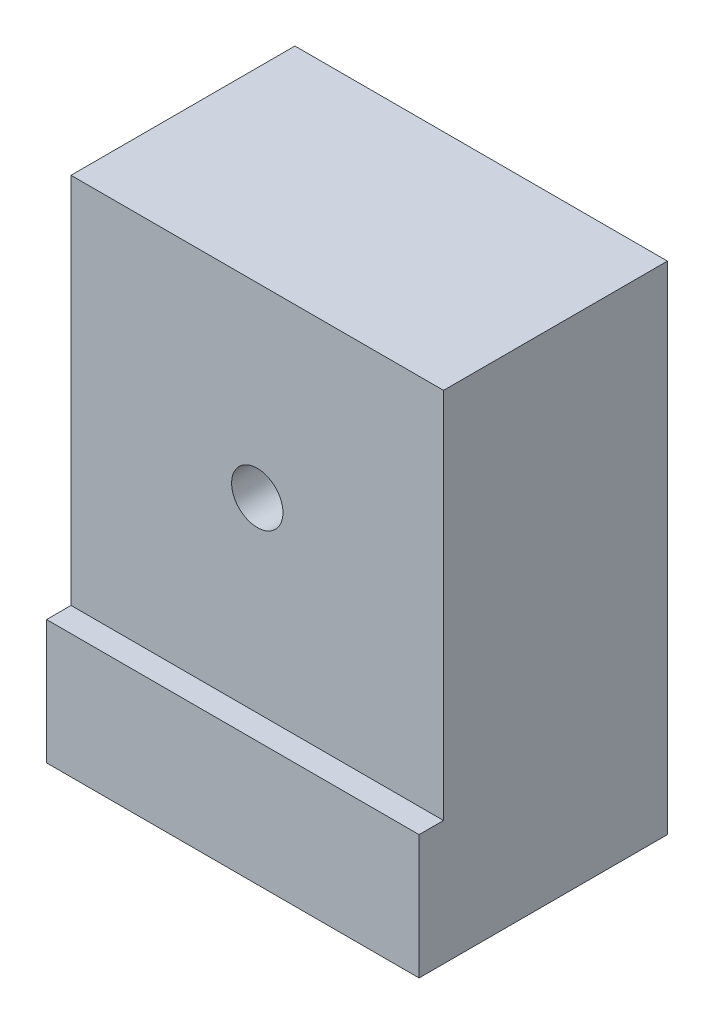
SolidWorks part; units mm, degrees
ref_plane "Front Plane" through (0, 0, 0) normal (0, 0, 1) x (1, 0, 0)
ref_plane "Top Plane" through (0, 0, 0) normal (0, 1, 0) x (1, 0, 0)
ref_plane "Right Plane" through (0, 0, 0) normal (1, 0, 0) x (0, 0, -1)
sketch "Sketch1" plane through (0, 0, 0) normal (0, 1, 0) x (1, 0, 0)
  line L1 (0, 0) -> (76.2, 0)
  line L2 (0, 0) -> (0, 50.8)
  line L3 (0, 50.8) -> (76.2, 50.8)
  line L4 (76.2, 0) -> (76.2, 50.8)
  dimension "D1" = 76.2
  dimension "D2" = 50.8
extrude "Boss-Extrude1" add sketch "Sketch1" along normal blind 101.6
sketch "Sketch2" plane through (0, 0, 0) normal (0, 0, 1) x (1, 0, 0)
  line L1 (0, 0) -> (38.1, 0)
  line L2 (0, 0) -> (0, 63.5)
  line L3 (0, 63.5) -> (38.1, 63.5)
  line L4 (38.1, 0) -> (38.1, 63.5)
  circle A0 centre (38.1, 63.5) radius 5.25
  dimension "D1" = 38.1
  dimension "D2" = 63.5
extrude "Cut-Extrude1" cut sketch "Sketch2" against normal blind 300 contours A0
sketch "Sketch3" plane through (0, 0, 0) normal (0, 0, 1) x (1, 0, 0)
  line L0 (76.2, 101.6) -> (76.2, 0) construction
  line L1 (0, 101.6) -> (76.2, 101.6)
  line L2 (0, 101.6) -> (0, 25.4)
  line L3 (0, 25.4) -> (76.2, 25.4)
  line L4 (76.2, 101.6) -> (76.2, 25.4)
  dimension "D1" = 76.2
extrude "Cut-Extrude2" cut sketch "Sketch3" against normal blind 5
